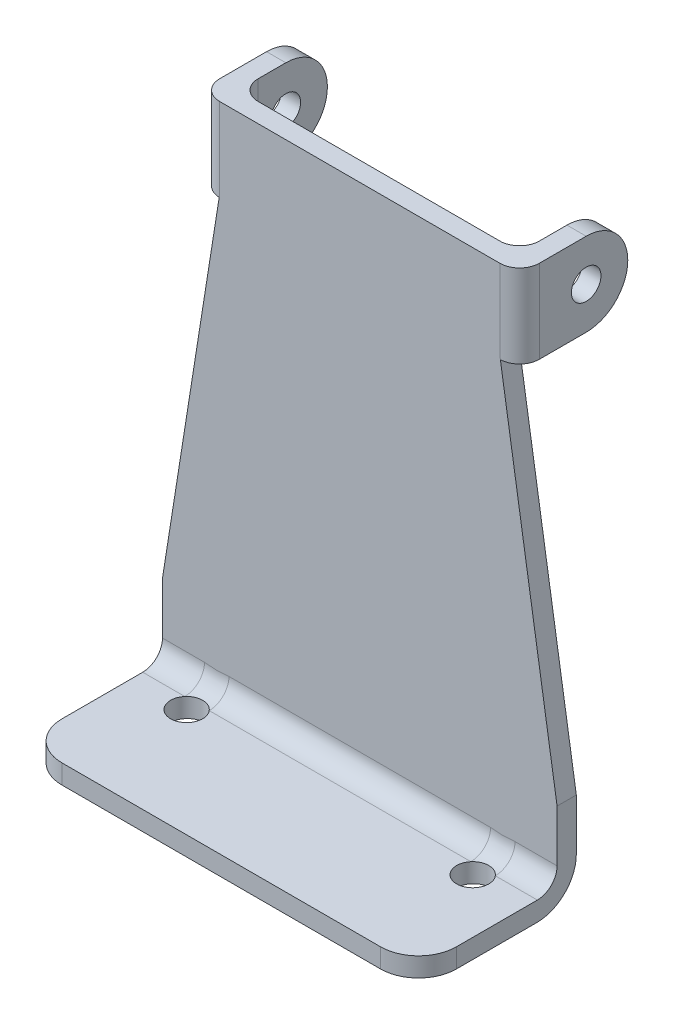
SolidWorks part; units mm, degrees
ref_plane "Front Plane" through (0, 0, 0) normal (0, 0, 1) x (1, 0, 0)
ref_plane "Top Plane" through (0, 0, 0) normal (0, 1, 0) x (1, 0, 0)
ref_plane "Right Plane" through (0, 0, 0) normal (1, 0, 0) x (0, 0, -1)
sketch "Sketch1" plane through (0, 0, 0) normal (0, 1, 0) x (1, 0, 0)
  line L0 (-20, 3) -> (20, 3) construction
  line L1 (-16.15, -8) -> (16.15, -8)
  line L2 (-20, -4.15) -> (-20, 8)
  line L3 (-20, 8) -> (20, 8)
  line L4 (20, -4.15) -> (20, 8)
  line L5 (-20, -8) -> (20, 8) construction
  line L6 (-20, 8) -> (20, -8) construction
  line L7 (0, 8) -> (0, -8) construction
  arc A0 (-16.15, -8) -> (-20, -4.15) centre (-16.15, -4.15) cw
  arc A1 (16.15, -8) -> (20, -4.15) centre (16.15, -4.15) ccw
  circle A2 centre (-14.5, 3) radius 1.625
  circle A3 centre (14.5, 3) radius 1.625
  point P0 (0, 0)
  dimension "D2" = 3.85
  dimension "D5" = 3.25
  dimension "D1" = 16
  dimension "D3" = 5
  dimension "D4" = 40
  dimension "D6" = 5.5
extrude "Boss-Extrude1" add sketch "Sketch1" along normal blind 1.95
sketch "Sketch3" plane through (0, 0, -8) normal (0, 0, -1) x (-1, 0, 0)
  line L0 (20, 1.95) -> (20, 0) construction
  line L1 (-20, 1.95) -> (20, 1.95)
  line L2 (-20, 1.95) -> (-20, 9.2)
  line L3 (-20, 9.2) -> (0, 9.2) construction
  line L4 (20, 1.95) -> (20, 9.2)
  line L5 (0, 53.95) -> (0, 9.2) construction
  line L6 (-14.25, 9.2) -> (0, 9.2) construction
  line L7 (-14.25, 45.516) -> (-14.25, 53.95)
  line L8 (-14.25, 53.95) -> (14.25, 53.95)
  line L9 (14.25, 45.516) -> (14.25, 53.95)
  line L10 (-14.25, 45.516) -> (-20, 9.2)
  line L11 (14.25, 45.516) -> (20, 9.2)
  point P15 (0, 0)
  dimension "D1" = 7.25
  dimension "D2" = 28.5
  dimension "D3" = 44.75
  dimension "D4" = 8.434
extrude "Boss-Extrude2" add sketch "Sketch3" against normal blind 1.95
fillet "Fillet1" radius 4 1 edges at (0, 0, -8)
fillet "Fillet2" radius 2 1 edges at (0, 1.95, -6.05)
sketch "Sketch4" plane through (14.25, 0, 0) normal (1, 0, 0) x (0, 0, -1)
  line L0 (6.05, 53.95) -> (8, 53.95) construction
  line L1 (6.05, 45.516) -> (12.8, 45.516)
  line L2 (6.05, 45.516) -> (6.05, 53.95)
  line L3 (6.05, 53.95) -> (12.8, 53.95)
  line L4 (12.8, 53.95) -> (12.8, 45.516) construction
  arc A0 (12.8, 45.516) -> (12.8, 53.95) centre (12.8, 49.733) ccw
  arc A1 (12.8, 45.516) -> (12.8, 53.95) centre (12.8, 49.733) ccw
  circle A2 centre (12.8, 49.733) radius 1.5
  line M7 (8, 45.516) -> (8, 53.95)
  line M8 (8, 53.95) -> (6.05, 53.95)
  line M9 (6.05, 53.95) -> (6.05, 45.516)
  line M10 (6.05, 45.516) -> (8, 45.516)
  dimension "D1" = 6.75
  dimension "D2" = 3
  dimension "D3" = 6.75
extrude "Boss-Extrude4" add sketch "Sketch4" along normal blind 1.95 contours M10 M7 M8 M9 | L4 L3 L1 A2 M7 | A0 L4 A2
ref_plane "Plane1" through (0, 0, 0) normal (1, 0, 0) x (0, 0, -1)
mirror "Mirror1" about plane through (0, 0, 0) normal (1, 0, 0) of "Boss-Extrude4"
fillet "Fillet3" radius 2 4 edges at (16.2, 49.733, -6.05) (-14.25, 49.733, -8) (-16.2, 49.733, -6.05) (14.25, 49.733, -8)
